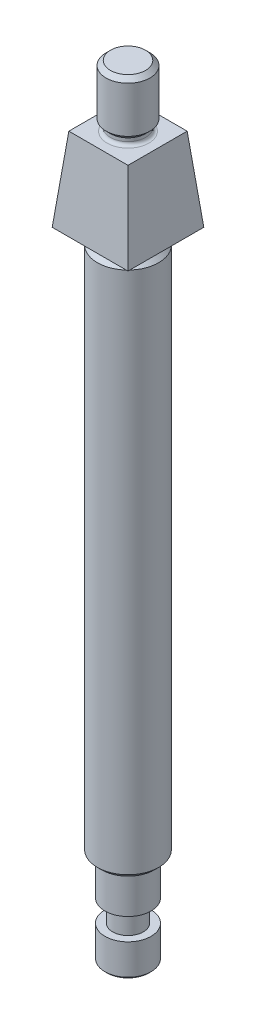
SolidWorks part; units mm, degrees
material "1.0050 (E295)"
ref_plane "Front Plane" through (0, 0, 0) normal (0, 0, 1) x (1, 0, 0)
ref_plane "Top Plane" through (0, 0, 0) normal (0, 1, 0) x (1, 0, 0)
ref_plane "Right Plane" through (0, 0, 0) normal (1, 0, 0) x (0, 0, -1)
sketch "Sketch1" plane through (0, 0, 0) normal (0, 1, 0) x (1, 0, 0)
  circle A0 centre (0, 0) radius 10.5
  dimension "D1" = 21
extrude "Boss-Extrude1" add sketch "Sketch1" along normal blind 42
sketch "Sketch3" plane through (0, 42, 0) normal (0, 1, 0) x (1, 0, 0)
  circle A0 centre (0, 0) radius 14
  dimension "D1" = 28
extrude "Boss-Extrude2" add sketch "Sketch3" along normal blind 243
sketch "Sketch4" plane through (0, 285, 0) normal (0, 1, 0) x (1, 0, 0)
  circle A0 centre (0, 0) radius 9
  dimension "D1" = 18
extrude "Boss-Extrude3" add sketch "Sketch4" along normal blind 5
sketch "Sketch5" plane through (0, 290, 0) normal (0, 1, 0) x (1, 0, 0)
  line L1 (-17.3, -17.3) -> (17.3, -17.3)
  line L2 (-17.3, -17.3) -> (-17.3, 17.3)
  line L3 (-17.3, 17.3) -> (17.3, 17.3)
  line L4 (17.3, -17.3) -> (17.3, 17.3)
  line L5 (-17.3, -17.3) -> (17.3, 17.3) construction
  line L6 (-17.3, 17.3) -> (17.3, -17.3) construction
  point P0 (0, 0)
  dimension "D1" = 34.6
  dimension "D2" = 34.6
extrude "Boss-Extrude4" add sketch "Sketch5" along normal blind 38 draft 5.711
sketch "Sketch6" plane through (0, 328, 0) normal (0, 1, 0) x (1, 0, 0)
  circle A0 centre (0, 0) radius 8
  dimension "D1" = 16
extrude "Boss-Extrude6" add sketch "Sketch6" along normal blind 3 contours A0
sketch "Sketch7" plane through (0, 331, 0) normal (0, 1, 0) x (1, 0, 0)
  circle A0 centre (0, 0) radius 10
  dimension "D1" = 20
extrude "Boss-Extrude7" add sketch "Sketch7" along normal blind 25
chamfer "Chamfer1" distance 2 angle 45 2 edges at (0, 331, 10) (0, 356, 10)
fillet "Fillet2" radius 2.5 2 edges at (0, 285, 9) (0, 290, 9)
sketch "Sketch8" plane through (0, 0, 0) normal (0, 0, 1) x (1, 0, 0)
  line L0 (-10.5, 42) -> (-10.5, 0) construction
  line L1 (-10.5, 25) -> (-7, 25)
  line L2 (-10.5, 25) -> (-10.5, 15)
  line L3 (-10.5, 15) -> (-7, 15)
  line L4 (-7, 25) -> (-7, 15)
  line L5 (-14, 42) -> (14, 42) construction
  point P6 (-10.5, 20)
  dimension "D1" = 10
  dimension "D2" = 7
  dimension "D3" = 22
revolve "Cut-Revolve1" cut sketch "Sketch8" angle 360 about axis through (0, 42, 0) along (0, -1, 0)
chamfer "Chamfer2" distance 2 angle 45 2 edges at (0, 42, 14) (0, 285, 14)
chamfer "Chamfer3" distance 1 angle 45 1 edges at (0, 0, 10.5)
fillet "Fillet3" radius 1.5 1 edges at (0, 328, 8)
equation "\"D3@Boss-Extrude4\"=atn(0.1)"
